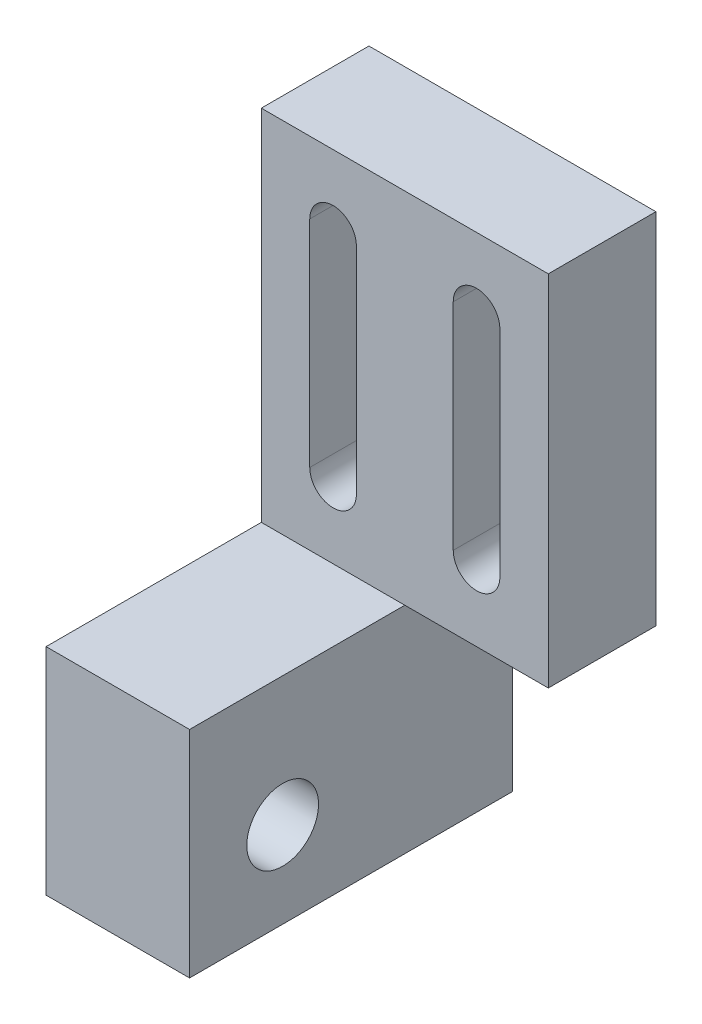
SolidWorks part; units mm, degrees
ref_plane "前视基准面" through (0, 0, 0) normal (0, 0, 1) x (1, 0, 0)
ref_plane "上视基准面" through (0, 0, 0) normal (0, 1, 0) x (1, 0, 0)
ref_plane "右视基准面" through (0, 0, 0) normal (1, 0, 0) x (0, 0, -1)
other "Configuration Table"
sketch "草图1" plane through (0, 0, 0) normal (0, 0, 1) x (1, 0, 0)
  line L0 (-84.56, 0.47) -> (-68.66, 0.47) construction
  line L1 (-84.56, 6.47) -> (-80.56, 6.47)
  line L2 (-84.56, 6.47) -> (-84.56, 0.47)
  line L3 (-84.56, 0.47) -> (-80.56, 0.47)
  line L4 (-80.56, 6.47) -> (-80.56, 0.47)
  dimension "D1" = 6
  dimension "D2" = 4
extrude "凸台-拉伸1" add sketch "草图1" along normal blind 9
sketch "草图5" plane through (0, 0, 0) normal (0, 0, 1) x (1, 0, 0)
  line L1 (-84.56, 6.47) -> (-76.56, 6.47)
  line L2 (-84.56, 6.47) -> (-84.56, 16.47)
  line L3 (-84.56, 16.47) -> (-76.56, 16.47)
  line L4 (-76.56, 6.47) -> (-76.56, 16.47)
  dimension "D1" = 10
  dimension "D2" = 8
extrude "凸台-拉伸3" add sketch "草图5" along normal blind 3
sketch "草图7" plane through (-84.56, 0, 0) normal (-1, 0, 0) x (0, 0, 1)
  line L6 (0, 16.47) -> (0, 0.47)
  line L7 (0, 0.47) -> (9, 0.47)
  line L8 (9, 0.47) -> (9, 6.47)
  line L9 (9, 6.47) -> (3, 6.47)
  line L10 (3, 6.47) -> (3, 16.47)
  line L11 (3, 16.47) -> (0, 16.47)
  line L12 (0, 16.47) -> (0, 0.47)
  line L13 (0, 0.47) -> (9, 0.47)
  line L14 (9, 0.47) -> (9, 6.47)
  line L15 (9, 6.47) -> (3, 6.47)
  line L16 (3, 6.47) -> (3, 16.47)
  line L17 (3, 16.47) -> (0, 16.47)
  arc A0 (5.755, 3.6299) -> (7.055, 3.6299) centre (6.405, 2.87) ccw construction
  arc A1 (5.755, 3.6299) -> (7.055, 3.6299) centre (6.405, 2.87) ccw
  circle A2 centre (6.405, 2.87) radius 1
  dimension "D2" = 2
  dimension "D1" = 0
extrude "切除-拉伸4" cut sketch "草图7" against normal through all contours A1 A2 region at (-84.56, 2.87, 6.405)
sketch "草图8" plane through (0, 0, 3) normal (0, 0, 1) x (1, 0, 0)
  line L0 (-82.56, 8.47) -> (-82.56, 14.47) construction
  line L1 (-83.21, 8.47) -> (-83.21, 14.47)
  line L2 (-81.91, 8.47) -> (-81.91, 14.47)
  line L3 (-78.56, 14.47) -> (-78.56, 8.47) construction
  line L4 (-77.91, 14.47) -> (-77.91, 8.47)
  line L5 (-79.21, 14.47) -> (-79.21, 8.47)
  line L6 (-80.56, 20.5485) -> (-80.56, 3.956) construction
  line L10 (-76.56, 6.47) -> (-76.56, 16.47) construction
  line L11 (-84.56, 16.47) -> (-84.56, 6.47) construction
  line L12 (-86.6279, 11.47) -> (-75.4887, 11.47) construction
  line L14 (-76.56, 16.47) -> (-84.56, 16.47) construction
  line L15 (-80.56, 6.47) -> (-76.56, 6.47) construction
  arc A0 (-83.21, 8.47) -> (-81.91, 8.47) centre (-82.56, 8.47) ccw
  arc A1 (-81.91, 14.47) -> (-83.21, 14.47) centre (-82.56, 14.47) ccw
  arc A2 (-77.91, 14.47) -> (-79.21, 14.47) centre (-78.56, 14.47) ccw
  arc A3 (-79.21, 8.47) -> (-77.91, 8.47) centre (-78.56, 8.47) ccw
  point P2 (-82.56, 11.47)
  point P8 (-78.56, 11.47)
  dimension "D1" = 1.3
  dimension "D2" = 2
  dimension "D3" = 4
extrude "切除-拉伸5" cut sketch "草图8" against normal through all
